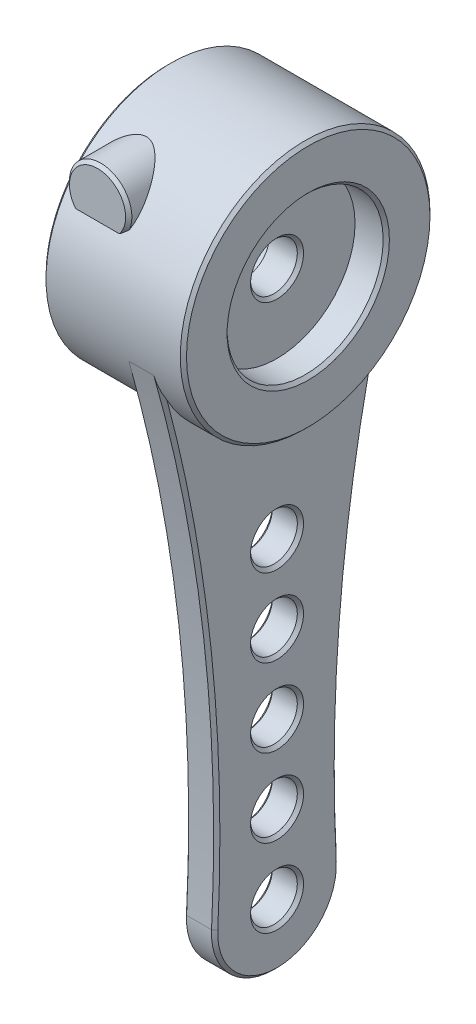
SolidWorks part; units mm, degrees
ref_plane "前视基准面" through (0, 0, 0) normal (0, 0, 1) x (1, 0, 0)
ref_plane "上视基准面" through (0, 0, 0) normal (0, 1, 0) x (1, 0, 0)
ref_plane "右视基准面" through (0, 0, 0) normal (1, 0, 0) x (0, 0, -1)
sketch "草图1" plane through (0, 0, 0) normal (1, 0, 0) x (0, 0, -1)
  circle A0 centre (0, 0) radius 8
  dimension "D1" = 16
extrude "凸台-拉伸1" add sketch "草图1" along normal blind 9
sketch "草图2" plane through (9, 0, 0) normal (1, 0, 0) x (0, 0, -1)
  circle A0 centre (0, 0) radius 5
  dimension "D1" = 10
extrude "切除-拉伸1" cut sketch "草图2" against normal blind 2
sketch "草图3" plane through (7, 0, 0) normal (1, 0, 0) x (0, 0, -1)
  circle A0 centre (0, 0) radius 1.5
  dimension "D1" = 3
extrude "切除-拉伸2" cut sketch "草图3" against normal blind 2
sketch "草图4" plane through (5, 0, 0) normal (1, 0, 0) x (0, 0, -1)
  circle A0 centre (0, 0) radius 3
  dimension "D1" = 6
extrude "切除-拉伸3" cut sketch "草图4" against normal blind 5
sketch "草图6" plane through (0, 0, 0) normal (0, 0, 1) x (1, 0, 0)
  line L0 (0, 8) -> (0, -8) construction
  circle A0 centre (2.5, 5) radius 2
  dimension "D1" = 4
  dimension "D2" = 2.5
  dimension "D3" = 5
extrude "凸台-拉伸2" add sketch "草图6" along normal blind 7
ref_plane "基准面1" through (5, 0, 0) normal (-1, 0, 0) x (0, 0, 1)
sketch "草图7" plane through (5, 0, 0) normal (-1, 0, 0) x (0, 0, 1)
  line L0 (0, 0) -> (0, -35) construction
  arc A0 (-3.9946, -34.7929) -> (3.9946, -34.7929) centre (0, -35) ccw
  arc A1 (-7.6934, -2.1937) -> (-3.9946, -34.7929) centre (-103.8605, -29.6143) cw
  circle A2 centre (0, 0) radius 8 construction
  arc A3 (7.6934, -2.1937) -> (3.9946, -34.7929) centre (103.8605, -29.6143) ccw
  circle A4 centre (0, -35) radius 1.5
  circle A5 centre (0, -30) radius 1.5
  circle A6 centre (0, -25) radius 1.5
  circle A7 centre (0, -20) radius 1.5
  circle A8 centre (0, -15) radius 1.5
  arc A9 (-7.6934, -2.1937) -> (7.6934, -2.1937) centre (0, 0) ccw
  dimension "D1" = 100
  dimension "D2" = 8
  dimension "D3" = 3
  dimension "D5" = 20
  dimension "D6" = 5
  dimension "D7" = 5
  dimension "D8" = 5
  dimension "D4" = 39
extrude "凸台-拉伸3" add sketch "草图7" against normal blind 2
chamfer "倒角1" distance 0.2 angle 45 6 edges at (2.5, 7, 7) (0, 0, -3) (0, 0, -8) (7, 0, -1.5) (9, 0, -5) (9, 0, -8)
chamfer "倒角2" distance 0.2 angle 45 16 edges at (5, -15, 1.5) (5, -20, 1.5) (5, -25, 1.5) (5, -30, 1.5) (5, -35, 1.5) (7, -15, 1.5) (7, -20, 1.5) (7, -25, 1.5) (7, -30, 1.5) (7, -35, 1.5) (5, -18.3405, -4.498) (5, -39, 0) (5, -18.3405, 4.498) (7, -18.3405, -4.498) (7, -39, 0) (7, -18.3405, 4.498)
move or copy body "实体-移动/复制1" [suppressed] bodies to move or copy 111
